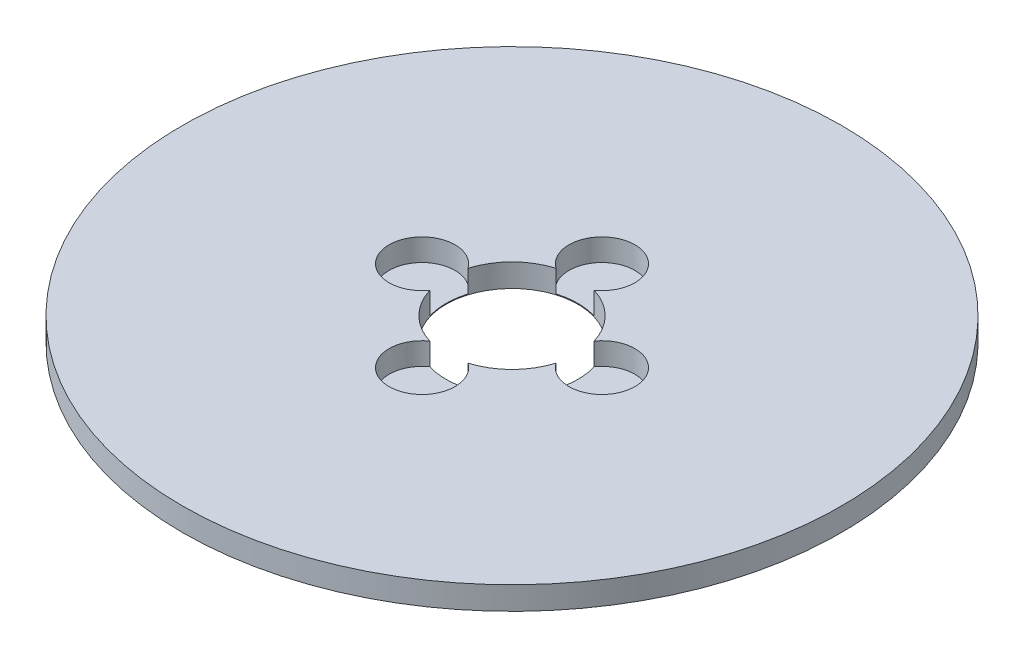
SolidWorks part; units mm, degrees
ref_plane "Front Plane" through (0, 0, 0) normal (0, 0, 1) x (1, 0, 0)
ref_plane "Top Plane" through (0, 0, 0) normal (0, 1, 0) x (1, 0, 0)
ref_plane "Right Plane" through (0, 0, 0) normal (1, 0, 0) x (0, 0, -1)
sketch "Sketch1" plane through (0, 0, 0) normal (0, 1, 0) x (1, 0, 0)
  circle A0 centre (0, 0) radius 100
  dimension "FLANGE_OD" = 200
extrude "Boss-Extrude1" add sketch "Sketch1" along normal blind 7
sketch "Sketch2" plane through (0, 0, 0) normal (0, 1, 0) x (1, 0, 0)
  circle A0 centre (0, 0) radius 20
  dimension "BORE_D" = 40
extrude "Cut-Extrude1" cut sketch "Sketch2" along normal through all
sketch "Sketch3" plane through (0, 7, 0) normal (0, 1, 0) x (1, 0, 0)
  circle A0 centre (0, 0) radius 27.2908 construction
  circle A1 centre (-27.2908, 0) radius 10
  dimension "BOLT_D" = 20
  dimension "BOLT_PCD" = 54.5815
extrude "Cut-Extrude2" cut sketch "Sketch3" against normal blind 6.7469
pattern_circular "CirPattern1" count 4 over 360 about axis through (0, 0, 0) along (0, 1, 0) of "Cut-Extrude2"
